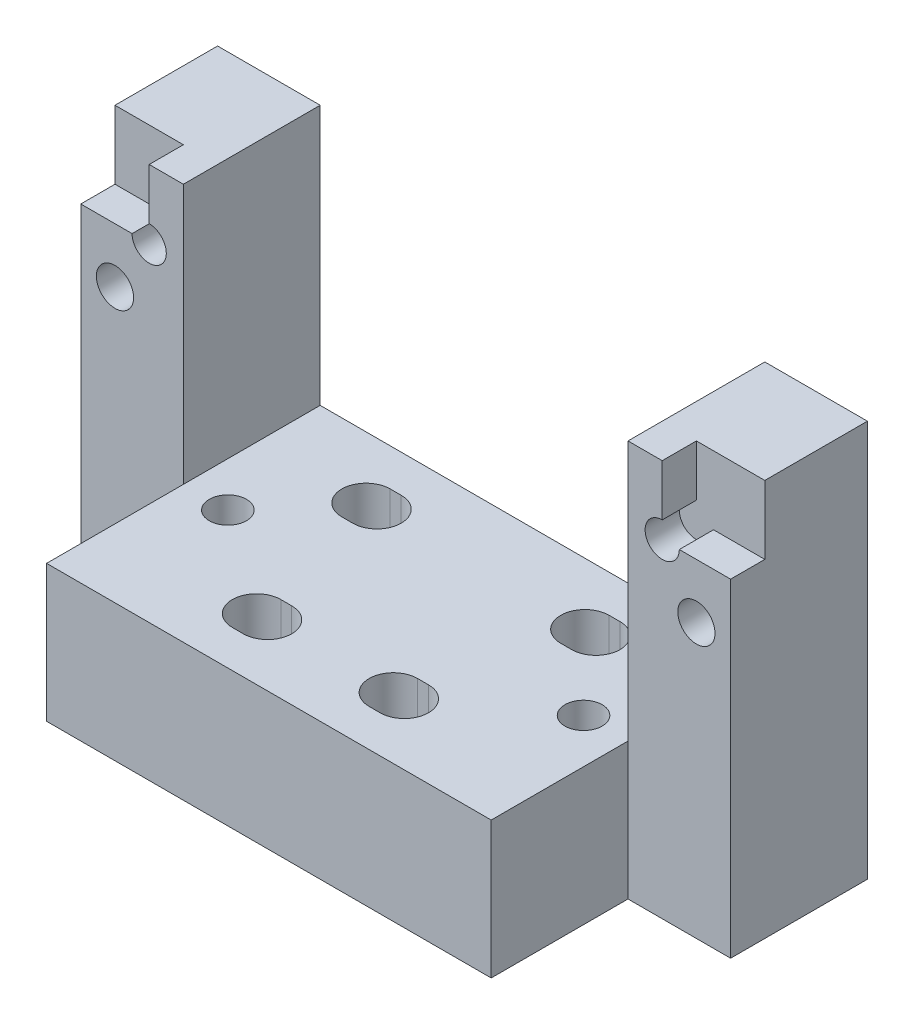
SolidWorks part; units mm, degrees
ref_plane "Front Plane" through (0, 0, 0) normal (0, 0, 1) x (1, 0, 0)
ref_plane "Top Plane" through (0, 0, 0) normal (0, 1, 0) x (1, 0, 0)
ref_plane "Right Plane" through (0, 0, 0) normal (1, 0, 0) x (0, 0, -1)
sketch "Sketch1" plane through (0, 0, 0) normal (0, 1, 0) x (1, 0, 0)
  line L1 (-30.1625, 12.7) -> (30.1625, 12.7)
  line L2 (-30.1625, 12.7) -> (-30.1625, -12.7)
  line L3 (-30.1625, -12.7) -> (30.1625, -12.7)
  line L4 (30.1625, 12.7) -> (30.1625, -12.7)
  line L5 (-30.1625, 12.7) -> (30.1625, -12.7) construction
  line L6 (-30.1625, -12.7) -> (30.1625, 12.7) construction
  point P0 (0, 0)
  dimension "D1" = 60.325
  dimension "D2" = 25.4
extrude "Boss-Extrude1" add sketch "Sketch1" along normal mid plane 36.83
sketch "Sketch2" plane through (0, 0, 12.7) normal (0, 0, 1) x (1, 0, 0)
  line L0 (-30.1625, 18.415) -> (30.1625, 18.415) construction
  line L1 (-20.6375, 18.415) -> (20.6375, 18.415)
  line L2 (-20.6375, 18.415) -> (-20.6375, -5.715)
  line L3 (-20.6375, -5.715) -> (20.6375, -5.715)
  line L4 (20.6375, 18.415) -> (20.6375, -5.715)
  line L5 (-30.1625, 18.415) -> (-30.1625, -18.415) construction
  line L6 (30.1625, 18.415) -> (30.1625, -18.415) construction
  line L7 (-30.1625, -18.415) -> (30.1625, -18.415) construction
  dimension "D1" = 9.525
  dimension "D2" = 9.525
  dimension "D3" = 12.7
extrude "Cut-Extrude1" cut sketch "Sketch2" against normal through all
sketch "Sketch3" plane through (30.1625, 0, 0) normal (1, 0, 0) x (0, 0, -1)
  line L0 (-12.7, 18.415) -> (12.7, 18.415) construction
  line L1 (-12.7, -18.415) -> (0, -18.415)
  line L2 (-12.7, -18.415) -> (-12.7, 18.415)
  line L3 (-12.7, 18.415) -> (0, 18.415)
  line L4 (0, -18.415) -> (0, 18.415)
  dimension "D1" = 0
extrude "Cut-Extrude2" cut sketch "Sketch3" against normal blind 9.525
sketch "Sketch4" plane through (0, 0, 0) normal (0, 0, 1) x (1, 0, 0)
  line L1 (30.1625, 18.415) -> (23.8125, 18.415)
  line L2 (30.1625, 18.415) -> (30.1625, 12.065)
  line L3 (30.1625, 12.065) -> (23.8125, 12.065)
  line L4 (23.8125, 18.415) -> (23.8125, 12.065)
  dimension "D1" = 6.35
  dimension "D2" = 6.35
extrude "Cut-Extrude3" cut sketch "Sketch4" against normal blind 3.175
sketch "Sketch5" plane through (0, 0, 0) normal (0, 0, 1) x (1, 0, 0)
  circle A0 centre (23.8125, 12.065) radius 1.5875
extrude "Cut-Extrude4" cut sketch "Sketch5" against normal blind 3.175
hole_wizard "#8-32 Tapped Hole1" positions "Sketch7" profile "Sketch6" tap size "#8-32" standard "ANSI Inch" end condition up to next
sketch "Sketch7" plane through (0, 0, 0) normal (0, 0, 1) x (1, 0, 0)
  line L0 (30.1625, -18.415) -> (30.1625, 12.065) construction
  line L1 (30.1625, 18.415) -> (23.8125, 18.415) construction
  point P0 (26.9875, 6.985)
  dimension "D1" = 3.175
  dimension "D2" = 11.43
sketch "Sketch6" plane through (26.9875, 6.985, 0) normal (1, 0, 0) x (0, -1, 0)
  line L0 (0, 0) -> (0, 12.701)
  line L1 (0, 12.701) -> (1.7272, 12.701)
  line L2 (1.7272, 12.701) -> (1.7272, 0)
  line L5 (1.7272, 0) -> (0, 0)
  line L11 (0, -6.35) -> (0, 107.95) construction
  dimension "Thru Tap Drill Dia." = 3.4544
  dimension "Thru Tap Drill Depth" = 12.701
cosmetic thread "Hole Thread1" parameters "D2"=4.1656
mirror "Mirror1" about plane through (0, 0, 0) normal (1, 0, 0) of "#8-32 Tapped Hole1", "Cut-Extrude4", "Cut-Extrude3", "Cut-Extrude2"
hole_wizard "#8-32 Tapped Hole2" positions "Sketch9" profile "Sketch8" tap size "#8-32" standard "ANSI Inch" end condition up to next
sketch "Sketch9" plane through (0, -18.415, 0) normal (0, -1, 0) x (-1, 0, 0)
  point P0 (16.51, 0)
  dimension "D1" = 16.51
sketch "Sketch8" plane through (-16.51, -18.415, 0) normal (1, 0, 0) x (0, 0, -1)
  line L0 (0, 0) -> (0, 12.701)
  line L1 (0, 12.701) -> (1.7272, 12.701)
  line L2 (1.7272, 12.701) -> (1.7272, 0)
  line L5 (1.7272, 0) -> (0, 0)
  line L11 (0, -6.35) -> (0, 107.95) construction
  dimension "Thru Tap Drill Dia." = 3.4544
  dimension "Thru Tap Drill Depth" = 12.701
cosmetic thread "Hole Thread2" parameters "D2"=4.1656
hole_wizard "CBORE SLOT for #8 Socket Head Cap Screw1" positions "Sketch11" profile "Sketch10" size "#8" standard "ANSI Inch" slot yes end condition up to next
sketch "Sketch11" plane through (0, -18.415, 0) normal (0, -1, 0) x (-1, 0, 0)
  line L2 (9.1059, -6.985) -> (3.5941, -6.985) construction
  point P0 (6.35, -6.985)
  point P2 (-6.35, -6.985)
  point P4 (-10.16, 6.985)
  point P6 (10.16, 6.985)
  dimension "D1" = 6.35
  dimension "D2" = 6.35
  dimension "D3" = 10.16
  dimension "D4" = 10.16
  dimension "D5" = 6.985
  dimension "D6" = 6.985
  dimension "D7" = 5.5118
sketch "Sketch10" plane through (-6.35, -18.415, 6.985) normal (1, 0, 0) x (0, 0, -1)
  line L0 (0, 0) -> (0, 12.7)
  line L1 (0, 12.7) -> (2.2479, 12.7)
  line L3 (2.2479, 12.7) -> (2.2479, 4.1656)
  line L4 (2.2479, 4.1656) -> (3.9687, 4.1656)
  line L5 (3.9687, 4.1656) -> (3.9688, 0)
  line L7 (3.9688, 0) -> (0, 0)
  line L11 (0, -6.35) -> (0, 107.95) construction
  dimension "Thru Hole Dia." = 4.4958
  dimension "Thru Hole Depth" = 12.7
  dimension "C'Bore Dia." = 7.9375
  dimension "C'Bore Depth" = 4.1656
mirror "Mirror2" about plane through (0, 0, 0) normal (1, 0, 0) of "#8-32 Tapped Hole2"
